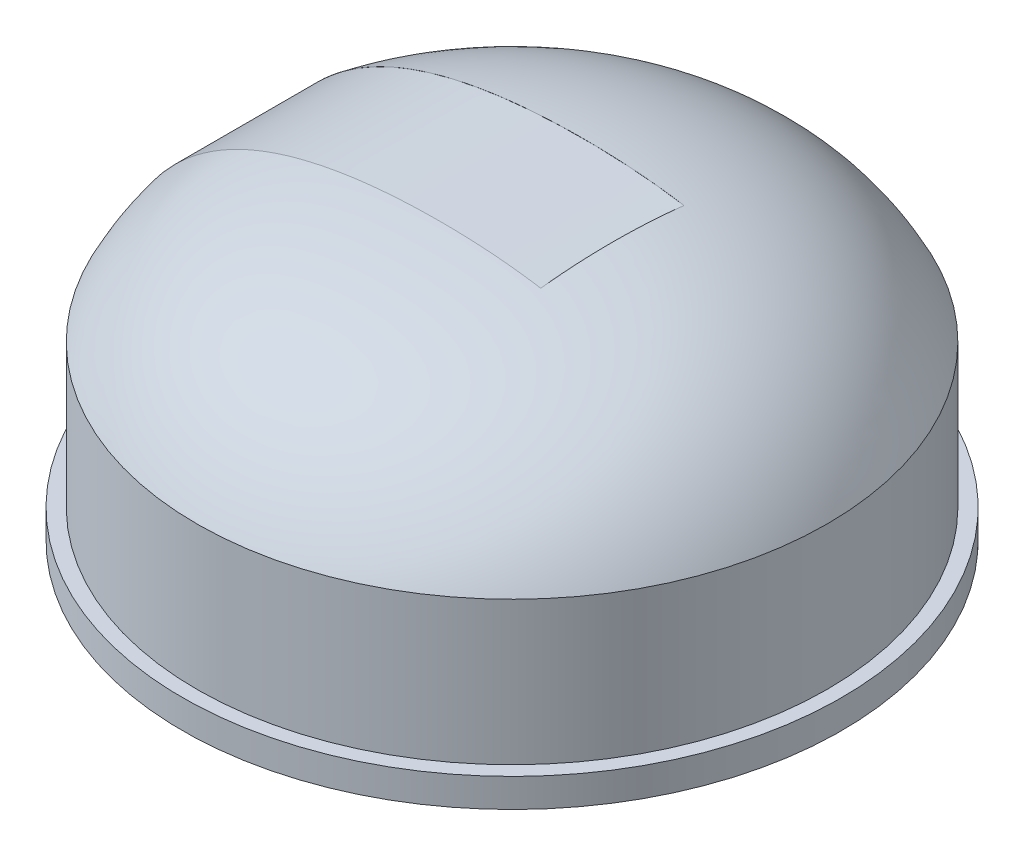
SolidWorks part; units mm, degrees
material "ABS"
ref_plane "Front Plane" through (0, 0, 0) normal (0, 0, 1) x (1, 0, 0)
ref_plane "Top Plane" through (0, 0, 0) normal (0, 1, 0) x (1, 0, 0)
ref_plane "Right Plane" through (0, 0, 0) normal (1, 0, 0) x (0, 0, -1)
sketch "Suction Cup Profile" plane through (0, 0, 0) normal (0, 0, 1) x (1, 0, 0)
  line L0 (0, 0) -> (0, 22) construction
  line L1 (0, 0) -> (-23, 0)
  line L2 (-23, 0) -> (-23, 2)
  line L3 (-23, 2) -> (-22, 2)
  line L4 (-22, 2) -> (-22, 12)
  line L5 (8.8234, 22) -> (-8.8234, 22) construction
  line L6 (0, 0) -> (0, 22)
  spline S0 degree 3 poles (-22, 12) (-18.4218, 19.0515) (-11.0292, 22) (0, 22) knots 0 0 0 0 1 1 1 1
  dimension "D1" = 23
  dimension "D2" = 2
  dimension "D3" = 1
  dimension "D4" = 10
  dimension "D5" = 22
revolve "Suction Cup Revolve" add sketch "Suction Cup Profile" angle 360 about L6
sketch "Lever Slot Profile" plane through (0, 0, 0) normal (0, 0, 1) x (1, 0, 0)
  line L0 (7, 10) -> (-20, 10)
  line L1 (-20, 10) -> (-20, 2)
  line L2 (23, 2) -> (-23, 2) construction
  line L3 (-20, 2) -> (-23, 2)
  line L4 (-23, 2) -> (-23, 26)
  line L5 (-23, 26) -> (7, 26)
  line L6 (7, 26) -> (7, 10)
  line L7 (-23, 0) -> (23, 0) construction
  line L8 (-22, 12) -> (-22, 2) construction
  dimension "D1" = 10
  dimension "D2" = 2
  dimension "D3" = 30
  dimension "D4" = 24
  dimension "D5" = 7
extrude "Lever Slot Cut" cut sketch "Lever Slot Profile" against normal blind 5 and the other way blind 5
fillet "Lever Slot Fillet" radius 1 3 edges at (7, 10, 0) (-20, 2, 0) (-20, 10, 0)
sketch "Cup Plunger Profile" plane through (0, 10, 0) normal (0, 1, 0) x (1, 0, 0)
  line L1 (3, 2) -> (-3, 2)
  line L2 (3, 2) -> (3, -2)
  line L3 (3, -2) -> (-3, -2)
  line L4 (-3, 2) -> (-3, -2)
  line L5 (3, 2) -> (-3, -2) construction
  line L6 (3, -2) -> (-3, 2) construction
  point P0 (0, 0)
  dimension "D1" = 4
  dimension "D2" = 6
extrude "Cup Plunger Cut" cut sketch "Cup Plunger Profile" against normal through all
sketch "Pad Slot Profile" plane through (0, 0, 0) normal (0, 0, 1) x (1, 0, 0)
  line L0 (0, 0) -> (0, 19.8107) construction
  line L1 (-20, 3) -> (-20, 9) construction
  line L2 (0, 9.5) -> (-17.5, 9.5)
  line L3 (0, 9.5) -> (0, -2.5)
  line L4 (0, -2.5) -> (-19.5, -2.5)
  line L5 (-19.5, 7.5) -> (-19.5, -2.5)
  line L6 (-19, 10) -> (6, 10) construction
  arc A0 (-19.5, 7.5) -> (-17.5, 9.5) centre (-17.5, 7.5) cw
  point P13 (-19.5, 9.5)
  dimension "D4" = 2
  dimension "D1" = 0.5
  dimension "D2" = 0.5
  dimension "D3" = 12
revolve "Pad Cut Profile" cut sketch "Pad Slot Profile" angle 360 about L0
sketch "Lever Extrude Profile" plane through (0, 0, 0) normal (0, 0, 1) x (1, 0, 0)
  line L5 (-19, 10) -> (6, 10)
  line L6 (7, 11) -> (7, 21.2423)
  line L7 (-21.4243, 12) -> (-21.4243, 2)
  line L8 (-21.4243, 2) -> (-21, 2)
  line L9 (-20, 3) -> (-20, 9)
  line L10 (-19, 10) -> (6, 10)
  line L11 (7, 11) -> (7, 21.2423)
  line L12 (-21.4243, 12) -> (-21.4243, 2)
  line L13 (-21.4243, 2) -> (-21, 2)
  line L14 (-20, 3) -> (-20, 9)
  arc A3 (6, 10) -> (7, 11) centre (6, 11) ccw
  arc A4 (-21, 2) -> (-20, 3) centre (-21, 3) ccw
  arc A5 (-19, 10) -> (-20, 9) centre (-19, 9) ccw
  arc A6 (6, 10) -> (7, 11) centre (6, 11) ccw
  arc A7 (-21, 2) -> (-20, 3) centre (-21, 3) ccw
  arc A8 (-19, 10) -> (-20, 9) centre (-19, 9) ccw
  spline S1 degree 3 poles (-4328.3013, -6686.4872) (193.0698, -256.1654) (93.6624, 16.0634) (1.7089, 21.76) (0.387, 21.7859) (-2.251, 21.7374) (-3.5672, 21.6626) (-6.1925, 21.3868) (-7.5017, 21.186) (-10.1099, 20.6049) (-11.3839, 20.2296) (-13.2284, 19.4984) (-13.8324, 19.2265) (-15.0149, 18.6164) (-15.5968, 18.2757) (-17.2592, 17.1635) (-18.2644, 16.2998) (-19.3789, 15.0519) (-19.5949, 14.7935) (-20.0076, 14.2661) (-82.0868, -70.5569) (713.8128, -728.2887) (-6833.099, 4185.2302) knots -8.424926 -8.424926 -8.424926 -8.424926 0.125 0.125 0.25 0.25 0.375 0.375 0.5 0.5 0.625 0.625 0.6875 0.6875 0.75 0.75 0.875 0.875 0.90625 0.90625 0.9375 10.734571 10.734571 10.734571 10.734571 only from (7, 21.2423) to (-21.4243, 12)
  spline S2 degree 3 poles (7, 21.2423) (5.6857, 21.4568) (4.3589, 21.5958) (1.7089, 21.76) (0.387, 21.7859) (-2.251, 21.7374) (-3.5672, 21.6626) (-6.1925, 21.3868) (-7.5017, 21.186) (-10.1099, 20.6049) (-11.3839, 20.2296) (-13.2284, 19.4984) (-13.8324, 19.2265) (-15.0149, 18.6164) (-15.5968, 18.2757) (-17.2592, 17.1635) (-18.2644, 16.2998) (-19.3789, 15.0519) (-19.5949, 14.7935) (-20.0076, 14.2661) (-20.5998, 13.457) (-21.1139, 12.5957) (-21.4243, 12) knots 0 0 0 0 0.125 0.125 0.25 0.25 0.375 0.375 0.5 0.5 0.625 0.625 0.6875 0.6875 0.75 0.75 0.875 0.875 0.90625 0.90625 0.9375 1 1 1 1
  dimension "D1" = 0
extrude "Lever Extrude" add sketch "Lever Extrude Profile" along normal blind 5 and the other way blind 5 separate body
sketch "Finger Catch Profile" plane through (-21.4243, 0, 0) normal (-1, 0, 0) x (0, 0, 1)
  line L0 (-5, 12) -> (-5, 2) construction
  line L1 (-5, 4) -> (5, 4)
  line L2 (-5, 4) -> (-5, 2)
  line L3 (-5, 2) -> (5, 2)
  line L4 (5, 4) -> (5, 2)
  dimension "D1" = 2
extrude "Finger Catch" add sketch "Finger Catch Profile" along normal blind 3
fillet "Finger Catch Fillet" radius 3 2 edges at (-24.4243, 3, 5) (-24.4243, 3, -5)
sketch "Lever Shape Profile" plane through (0, 0, 5) normal (0, 0, 1) x (1, 0, 0)
  line L0 (-19, 10) -> (6, 10) construction
  line L1 (2.5609, 10) -> (-19, 10)
  line L2 (-21.4243, 4) -> (-21.4243, 2) construction
  line L3 (-21.4243, 2) -> (-21, 2) construction
  arc A0 (-20, 9) -> (-19, 10) centre (-19, 9) cw
  spline S0 degree 3 poles (-20, 9) (-19.9602, 10.609) (-19.9675, 11.9922) (-15.5656, 17.8574) (-9.8051, 19.631) (-0.4719, 20.8335) (0.8057, 15.4089) (0.4617, 11.4776) (2.5609, 10) knots 0 0 0 0 0.074344 0.186491 0.469323 0.695905 0.824059 1 1 1 1
  line M8 (-19, 10) -> (6, 10)
  dimension "D1" = 1.7374
  dimension "D2" = 4.2543
  dimension "D3" = 12.9839
  dimension "D4" = 20.6231
  dimension "D5" = 21.9238
  dimension "D6" = 23.9852
  dimension "D7" = 9.8624
  dimension "D8" = 13.4172
  dimension "D9" = 13.7512
  dimension "D10" = 17.2668
  dimension "D11" = 17.6396
extrude "Lever Shape Cut" cut sketch "Lever Shape Profile" against normal blind 10 contours S0 A0 M8 region at (-8.3349, 14.3384, 5)
fillet "Lever Fillet" radius 2 1 edges at (2.5609, 10, 0)
sketch "Pin Hole Profile" plane through (0, 0, 5) normal (0, 0, 1) x (1, 0, 0)
  line L0 (7, 11) -> (7, 21.2423) construction
  line L1 (3.2959, 10) -> (6, 10) construction
  circle A0 centre (4, 17) radius 0.5
  dimension "D1" = 1
  dimension "D2" = 3
  dimension "D3" = 7
extrude "Pin Hole Cut" cut sketch "Pin Hole Profile" against normal blind 10
sketch "Plunger Slot Profile" plane through (7, 0, 0) normal (1, 0, 0) x (0, 0, -1)
  line L0 (0, 21.2423) -> (0, 11) construction
  line L1 (5, 21.2423) -> (-5, 21.2423) construction
  line L2 (5, 11) -> (-5, 11) construction
  line L4 (-2, 19.2423) -> (2, 19.2423)
  line L5 (-2, 19.2423) -> (-2, 9.2423)
  line L6 (-2, 9.2423) -> (2, 9.2423)
  line L7 (2, 19.2423) -> (2, 9.2423)
  line L8 (-2, 19.2423) -> (2, 9.2423) construction
  line L9 (-2, 9.2423) -> (2, 19.2423) construction
  point P6 (0, 14.2423)
  dimension "D1" = 10
  dimension "D2" = 2
  dimension "D3" = 4
extrude "Plunger Slot Cut" cut sketch "Plunger Slot Profile" against normal blind 10
